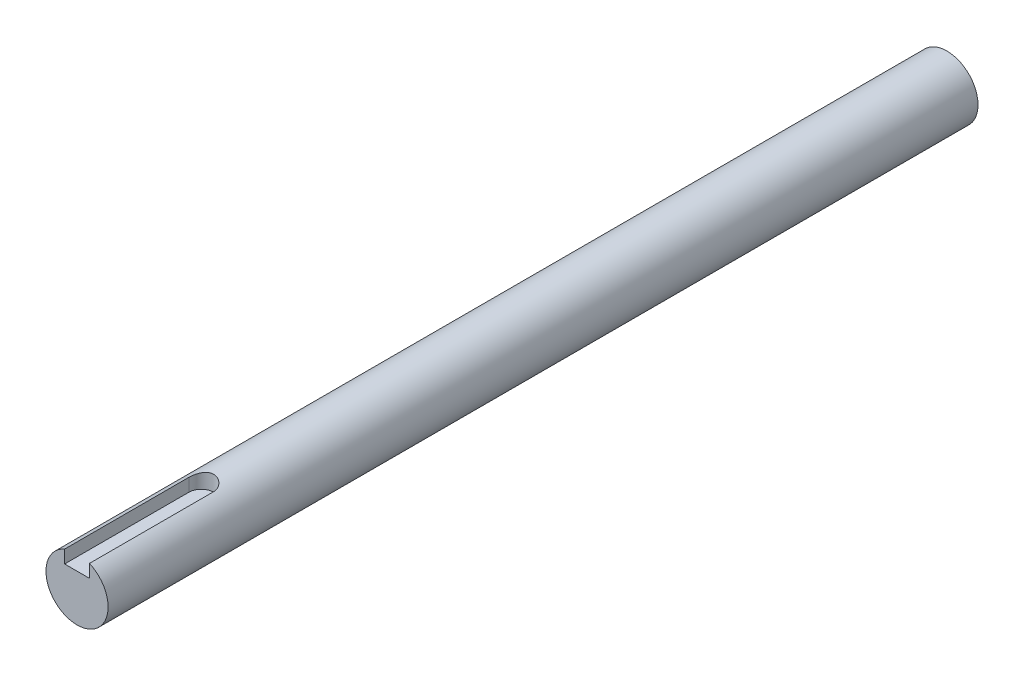
SolidWorks part; units mm, degrees
ref_plane "Front Plane" through (0, 0, 0) normal (0, 0, 1) x (1, 0, 0)
ref_plane "Top Plane" through (0, 0, 0) normal (0, 1, 0) x (1, 0, 0)
ref_plane "Right Plane" through (0, 0, 0) normal (1, 0, 0) x (0, 0, -1)
sketch "Sketch1" plane through (0, 0, 0) normal (0, 0, 1) x (1, 0, 0)
  line L0 (0, 0) -> (0, 5) construction
  line L1 (0, 2.5) -> (2, 2.5)
  line L2 (2, 2.5) -> (2, 4.5826)
  line L3 (0, 2.5) -> (-2, 2.5)
  line L4 (-2, 2.5) -> (-2, 4.5826)
  circle A0 centre (0, 0) radius 5
  dimension "D1" = 2.5
  dimension "D2" = 10
extrude "Boss-Extrude1" add sketch "Sketch1" along normal blind 20 contours L4 A0 L2 L1 L3 region at (0, -0.5042, 0)
extrude "Boss-Extrude2" add sketch "Sketch1<3>" against normal blind 120 contours A0
sketch "Sketch1<3>" plane through (0, 0, 0) normal (0, 0, 1) x (1, 0, 0) same geometry as "Sketch1"
sketch "Sketch2" plane through (0, 0, 0) normal (0, 0, 1) x (1, 0, 0)
  line L0 (0.1524, 3.7271) -> (0, 5)
  line L1 (0, 5) -> (0, 2.5)
  line L2 (0, 2.5) -> (2, 2.5)
  line L3 (2, 2.5) -> (2, 4.5826)
  line L4 (2, 4.5826) -> (2, 4.6052)
  line L5 (2, 4.6052) -> (0, 4.6052)
  line L6 (0, 4.6052) -> (0, 5)
sketch "Sketch4" plane through (0, 0, 0) normal (0, 0, 1) x (1, 0, 0)
  line L0 (0, 2.5) -> (2, 2.5)
  line L1 (2, 2.5) -> (2, 5.2011)
  line L2 (2, 5.2011) -> (0, 5.2011)
  line L3 (0, 5.2011) -> (0, 2.5)
revolve "Cut-Revolve2" cut sketch "Sketch4" angle 360 about L0
